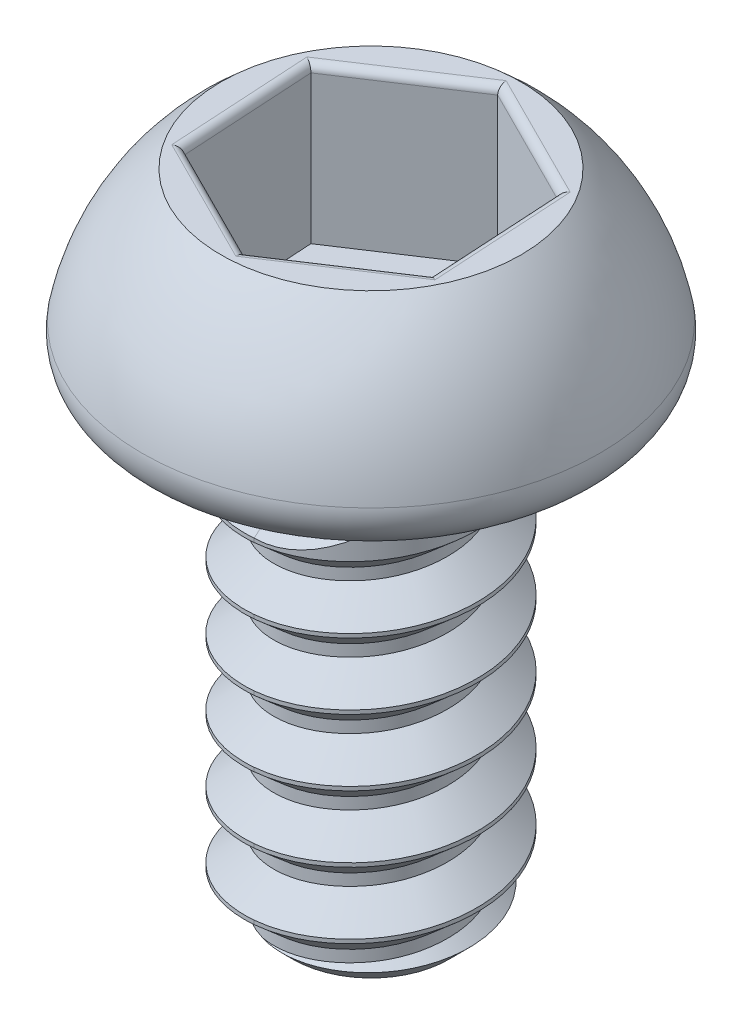
SolidWorks part; units mm, degrees
ref_plane "Piano frontale" through (0, 0, 0) normal (0, 0, 1) x (1, 0, 0)
ref_plane "Piano superiore" through (0, 0, 0) normal (0, 1, 0) x (1, 0, 0)
ref_plane "Piano destro" through (0, 0, 0) normal (1, 0, 0) x (0, 0, -1)
sketch "Schizzo4" plane through (0, 0, 0) normal (0, 0, 1) x (1, 0, 0)
  line L0 (3, 0) -> (1.5, 0)
  line L1 (1.5, 0) -> (1.5, -6)
  line L2 (1.5, -6) -> (0, -6)
  line L3 (0, 4.3167) -> (0, -10.8324) construction
  line L4 (0, 2.3) -> (0, -6)
  line L5 (1.9261, 2.3) -> (0, 2.3)
  arc A0 (1.9261, 2.3) -> (3, 0) centre (0, 0) cw
  dimension "D3" = 3
  dimension "D1" = 1.5
  dimension "D2" = 3
  dimension "D4" = 6
  dimension "D5" = 2.3
revolve "Rivoluzione1" add sketch "Schizzo4" angle 360 about L3
fillet "Raccordo2" radius 0.5 1 edges at (0, 0, 3)
sketch "Schizzo5" plane through (0, 2.3, 0) normal (0, 1, 0) x (1, 0, 0)
  line L1 (1.5481, -0.7767) -> (1.4467, 0.9524)
  line L2 (1.4467, 0.9524) -> (-0.1014, 1.7291)
  line L3 (-0.1014, 1.7291) -> (-1.5481, 0.7767)
  line L4 (-1.5481, 0.7767) -> (-1.4467, -0.9524)
  line L5 (-1.4467, -0.9524) -> (0.1014, -1.7291)
  line L6 (0.1014, -1.7291) -> (1.5481, -0.7767)
  circle A0 centre (0, 0) radius 1.5 construction
  dimension "D1" = 3
extrude "Taglio-Estrusione1" cut sketch "Schizzo5" against normal blind 2
fillet "Raccordo4" radius 0.1 6 edges at (-0.8248, 2.3, -1.2529) (-1.4974, 2.3, 0.0878) (-0.6726, 2.3, 1.3407) (0.8248, 2.3, 1.2529) (1.4974, 2.3, -0.0878) (0.6726, 2.3, -1.3407)
chamfer "Smusso2" distance 0.5 angle 45 1 edges at (0, -6, 1.5)
sketch "Schizzo6" plane through (0, -6, 0) normal (0, -1, 0) x (1, 0, 0)
  circle A0 centre (0, 0) radius 1.5 construction
  circle A1 centre (0, 0) radius 1.5
curve "Elica/Spirale1" pitch 0.85 height 5.7375 radius 1.5 centre (0, -6, 0) axis (0, 1, 0) start towards (1, 0, 0)
sketch "Schizzo8" plane through (0, 0, 0) normal (0, 0, 1) x (1, 0, 0)
  line L0 (1.5, -6) -> (1.5, -6.8)
  line L1 (1.5, -6.8) -> (1.125, -6.475)
  line L2 (1.125, -6.475) -> (1.125, -6.325)
  line L3 (1.125, -6.325) -> (1.5, -6)
  line L4 (1.5, -6.4) -> (1.125, -6.4) construction
  line L5 (1.5, -5.5) -> (1.5, 0) construction
  dimension "D1" = 0.375
  dimension "D2" = 0.8
  dimension "D3" = 0.15
sweep "Taglia-Sweep1" cut profiles "Schizzo8" path "Elica/Spirale1" align with end faces yes
sketch "Schizzo9" plane through (0, 0, 0) normal (-1, 0, 0) x (0, 0, 1)
  line L4 (1.125, -0.7375) -> (1.5, -1.0625)
  line L5 (1.5, -1.0625) -> (1.5, -0.2625)
  line L7 (1.125, -0.5875) -> (1.125, -0.7375)
  line L9 (1.5, -1.0625) -> (1.5, -0.2625)
  line L11 (1.125, -0.5875) -> (1.125, -0.7375)
  line L16 (1.125, -0.7375) -> (1.5, -1.0625)
  line L18 (1.5, -0.2625) -> (1.125, -0.5875)
  line L20 (1.5, -0.2625) -> (1.125, -0.5875)
  dimension "D1" = 0
extrude "Taglio-Estrusione2" cut sketch "Schizzo9" against normal blind 10
